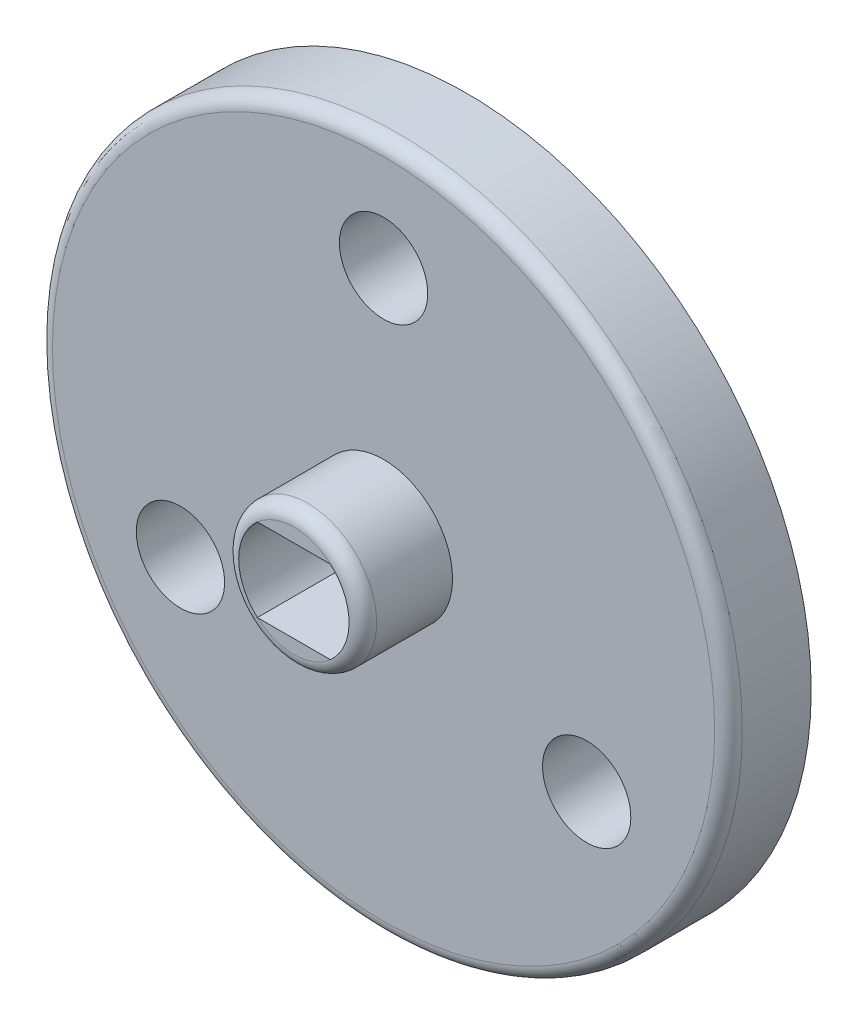
SolidWorks part; units mm, degrees
ref_plane "Ebene vorne" through (0, 0, 0) normal (0, 0, 1) x (1, 0, 0)
ref_plane "Ebene oben" through (0, 0, 0) normal (0, 1, 0) x (1, 0, 0)
ref_plane "Ebene rechts" through (0, 0, 0) normal (1, 0, 0) x (0, 0, -1)
sketch "Skizze1" plane through (0, 0, 0) normal (1, 0, 0) x (0, 0, -1)
  line L1 (96.5, 25) -> (96.5, 0) construction
  line L2 (90.5, 25) -> (90.5, 0) construction
  line L3 (0, 25) -> (99, 25) construction
  line L5 (96.5, 25) -> (96.5, 0)
  line L6 (90.5, 25) -> (90.5, 5)
  line L7 (90.5, 25) -> (96.5, 25)
  line L8 (84, 4) -> (84, 0) construction
  line L10 (84, 4) -> (84, 0)
  line L12 (0, 0) -> (99, 0) construction
  line L13 (84, 0) -> (96.5, 0)
  line L14 (84, 5) -> (84, 4) construction
  line L15 (90.5, 5) -> (84, 5) construction
  line L16 (84, 5) -> (84, 4)
  line L17 (90.5, 5) -> (84, 5)
revolve "Rotation1" add sketch "Skizze1" angle 360 about L13
sketch "Skizze2" plane through (0, 0, -96.5) normal (0, 0, -1) x (-1, 0, 0)
  line L0 (0, 0) -> (25, 0) construction
  line L1 (0, 0) -> (-450, 0) construction
  line L2 (2.6458, 3) -> (-2.6458, 3) construction
  line L3 (0, 0) -> (4, 0)
  line L4 (0, 0) -> (-4, 0)
  line L5 (2.6458, 3) -> (-2.6458, 3)
  arc A1 (-2.6458, 3) -> (-4, 0) centre (0, 0) ccw construction
  arc A2 (4, 0) -> (2.6458, 3) centre (0, 0) ccw construction
  arc A3 (-2.6458, 3) -> (-4, 0) centre (0, 0) ccw
  arc A4 (4, 0) -> (2.6458, 3) centre (0, 0) ccw
extrude "Schnitt-Linear austragen1" cut sketch "Skizze2" against normal through all
mirror "Spiegeln1" about plane through (0, 0, -84) normal (0, -1, 0) of "Schnitt-Linear austragen1"
sketch "Skizze3" plane through (0, 0, -96.5) normal (0, 0, -1) x (-1, 0, 0)
  circle A0 centre (0, 0) radius 17 construction
  point P4 (0, 17)
hole_wizard "Ø6.4 (6.4) Durchmesser Bohrung1" positions "Skizze3" profile "Skizze4" hole size "Ø6.4" standard "DIN"
sketch "Skizze4" plane through (0, 17, -96.5) normal (1, 0, 0) x (0, 1, 0)
  line L0 (0, 0) -> (0, 10.4228)
  line L1 (0, 10.4228) -> (3.2, 8.5)
  line L2 (3.2, 8.5) -> (3.2, 0)
  line L5 (3.2, 0) -> (0, 0)
  line L10 (0, 10.4228) -> (-3.2, 8.5) construction
  line L11 (0, -6.35) -> (0, 107.95) construction
  dimension "Bohrerdurchmesser" = 6.4
  dimension "Bohrungstiefe" = 8.5
  dimension "Spitzenwinkel" = 118
pattern_circular "Kreismuster1" count 3 over 360 of "Ø6.4 (6.4) Durchmesser Bohrung1" reverse direction yes
fillet "Verrundung1" radius 1 2 edges at (5, 0, -84) (25, 0, -90.5)
